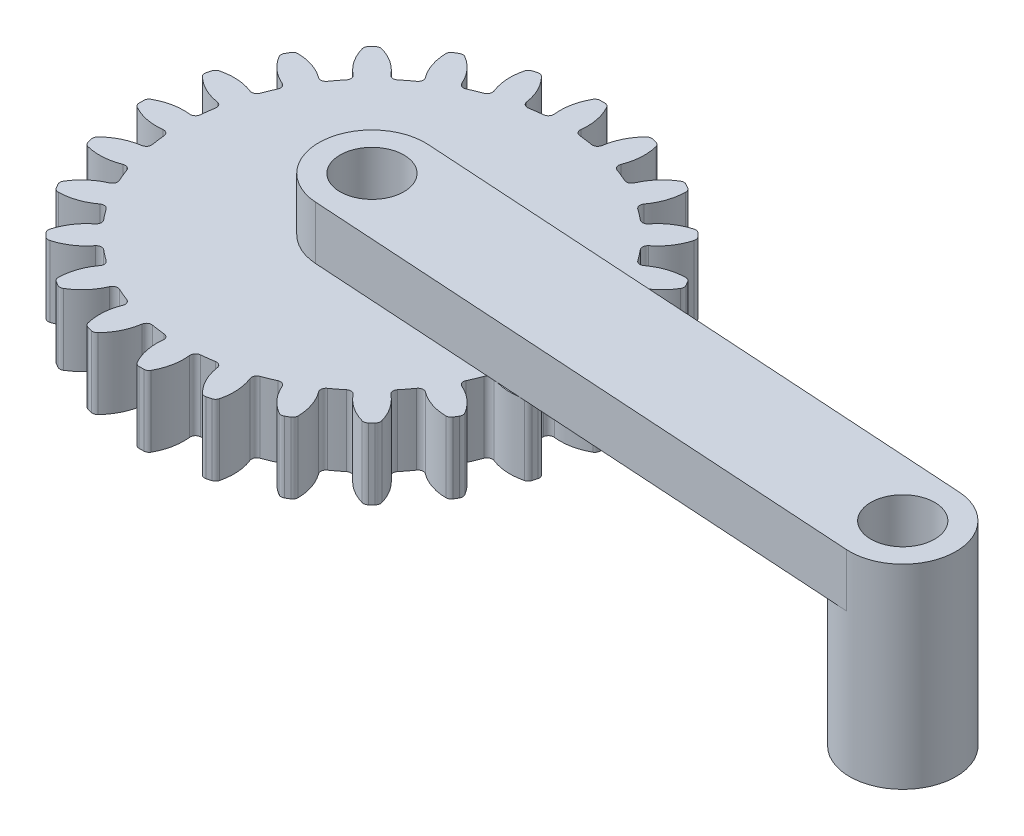
SolidWorks part; units mm, degrees
note: '?' marks a value the reader was unsure of. The reader was unsure of these and kept them because the rebuilt part matched: shared geometry of "Sketch2<5>".
ref_plane "Front Plane" through (0, 0, 0) normal (0, 0, 1) x (1, 0, 0)
ref_plane "Top Plane" through (0, 0, 0) normal (0, 1, 0) x (1, 0, 0)
ref_plane "Right Plane" through (0, 0, 0) normal (1, 0, 0) x (0, 0, -1)
sketch "Sketch2" plane through (0, 0, 0) normal (0, 1, 0) x (1, 0, 0)
  line L0 (0, 0) -> (0, 10.4648) construction
  line L1 (0.3, 13) -> (-0.3, 13)
  circle A0 centre (0, 0) radius 10.75
  circle A1 centre (0, 0) radius 13 construction
  arc A2 (-0.3, 13) -> (-0.7, 10.7272) centre (2.2248, 11.3841) ccw
  arc A3 (0.3, 13) -> (0.7, 10.7272) centre (-2.2248, 11.3841) cw
  circle A4 centre (0, 0) radius 2.55
  arc A5 (-0.7, 10.7272) -> (0.7, 10.7272) centre (0, 0) cw
  point P10 (0, 13)
  dimension "D1" = 21.5
  dimension "D2" = 26
  dimension "D5" = 5.1
  dimension "D3" = 0.6
  dimension "D4" = 0.7
extrude "Boss-Extrude1" add sketch "Sketch2" along normal blind 4
extrude "Boss-Extrude2" add sketch "Sketch2<5>" along normal blind 4 contours A3 L1 A2 A0
sketch "Sketch2<5>" plane through (0, 0, 0) normal (0, 1, 0) x (1, 0, 0) same geometry as "Sketch2"
pattern_circular "CirPattern2" count 24 over 360 about axis through (0, 0, 0) along (0, 1, 0) of "Boss-Extrude2"
sketch "Sketch3" plane through (0, 4, 0) normal (0, 1, 0) x (1, 0, 0)
  line L0 (31.9374, -2) -> (0, 0) construction
  line L1 (31.7499, -4.9941) -> (-0.1875, -2.9941)
  line L2 (32.1249, 0.9941) -> (0.1875, 2.9941)
  line L3 (0, 0) -> (16.4404, 0) construction
  arc A0 (31.7499, -4.9941) -> (32.1249, 0.9941) centre (31.9374, -2) ccw
  arc A1 (0.1875, 2.9941) -> (-0.1875, -2.9941) centre (0, 0) ccw
  circle A2 centre (0, 0) radius 1.8
  circle A3 centre (31.9374, -2) radius 1.8
  point P2 (15.9687, -1)
  dimension "D1" = 3
  dimension "D3" = 3.6
  dimension "D2" = 32
  dimension "D4" = 2
extrude "Boss-Extrude3" add sketch "Sketch3" along normal blind 3
sketch "Sketch4" plane through (0, 4, 0) normal (0, -1, 0) x (1, 0, 0)
  circle A0 centre (31.9374, 2) radius 1.8
  circle A1 centre (31.9374, 2) radius 3
  dimension "D1" = 3.6
extrude "Boss-Extrude4" add sketch "Sketch4" along normal blind 8
sketch "Sketch5" plane through (0, 4, 0) normal (0, -1, 0) x (1, 0, 0)
  circle A0 centre (0, 0) radius 1.8
  circle A1 centre (0, 0) radius 2.55
  dimension "D1" = 3.6
extrude "Boss-Extrude5" add sketch "Sketch5" along normal blind 3
fillet "Fillet1" radius 0.3 96 edges at (4.7574, 2, 9.64) (6.2402, 2, 11.4083) (6.7598, 2, 11.1083) (5.9698, 2, 8.94) (2.1003, 2, 10.5428) (3.0749, 2, 12.6347) (3.6544, 2, 12.4794) (3.4525, 2, 10.1805) (-0.7, 2, 10.7272) (-0.3, 2, 13) (0.3, 2, 13) (0.7, 2, 10.7272) (0.7, 2, -10.7272) (-3.4525, 2, 10.1805) (-3.6544, 2, 12.4794) (-3.0749, 2, 12.6347) (-2.1003, 2, 10.5428) (0.3, 2, -13) (-0.3, 2, -13) (-5.9698, 2, 8.94) (-6.7598, 2, 11.1083) (-6.2402, 2, 11.4083) (-4.7574, 2, 9.64) (-0.7, 2, -10.7272) (-8.0802, 2, 7.0903) (-9.4045, 2, 8.9803) (-8.9803, 2, 9.4045) (-7.0903, 2, 8.0802) (-9.64, 2, 4.7574) (-11.4083, 2, 6.2402) (-11.1083, 2, 6.7598) (-8.94, 2, 5.9698) (-10.5428, 2, 2.1003) (-12.6347, 2, 3.0749) (-12.4794, 2, 3.6544) (-10.1805, 2, 3.4525) (-10.7272, 2, -0.7) (-13, 2, -0.3) (-13, 2, 0.3) (-10.7272, 2, 0.7) (-10.1805, 2, -3.4525) (-12.4794, 2, -3.6544) (-12.6347, 2, -3.0749) (-10.5428, 2, -2.1003) (-8.94, 2, -5.9698) (-11.1083, 2, -6.7598) (-11.4083, 2, -6.2402) (-9.64, 2, -4.7574) (-7.0903, 2, -8.0802) (-8.9803, 2, -9.4045) (-9.4045, 2, -8.9803) (-8.0802, 2, -7.0903) (-4.7574, 2, -9.64) (-6.2402, 2, -11.4083) (-6.7598, 2, -11.1083) (-5.9698, 2, -8.94) (10.7272, 2, 0.7) (13, 2, 0.3) (13, 2, -0.3) (10.7272, 2, -0.7) (10.5428, 2, -2.1003) (12.6347, 2, -3.0749) (12.4794, 2, -3.6544) (10.1805, 2, -3.4525) (9.64, 2, -4.7574) (11.4083, 2, -6.2402) (11.1083, 2, -6.7598) (8.94, 2, -5.9698) (8.0802, 2, -7.0903) (9.4045, 2, -8.9803) (8.9803, 2, -9.4045) (7.0903, 2, -8.0802) (5.9698, 2, -8.94) (6.7598, 2, -11.1083) (6.2402, 2, -11.4083) (4.7574, 2, -9.64) (3.4525, 2, -10.1805) (3.6544, 2, -12.4794) (3.0749, 2, -12.6347) (2.1003, 2, -10.5428) (-2.1003, 2, -10.5428) (-3.0749, 2, -12.6347) (-3.6544, 2, -12.4794) (-3.4525, 2, -10.1805) (10.1805, 2, 3.4525) (12.4794, 2, 3.6544) (12.6347, 2, 3.0749) (10.5428, 2, 2.1003) (8.94, 2, 5.9698) (11.1083, 2, 6.7598) (11.4083, 2, 6.2402) (9.64, 2, 4.7574) (7.0903, 2, 8.0802) (8.9803, 2, 9.4045) (9.4045, 2, 8.9803) (8.0802, 2, 7.0903)
sketch "Sketch6" plane through (0, 0, 0) normal (0, -1, 0) x (1, 0, 0)
  circle A0 centre (0, 0) radius 1.8
  circle A1 centre (0, 0) radius 3
  dimension "D1" = 6
  dimension "D2" = 3.6
extrude "Boss-Extrude6" add sketch "Sketch6" along normal blind 4
sketch "Sketch7" plane through (0, 0, 0) normal (0, 0, 1) x (1, 0, 0)
  line L0 (-13, 0) -> (-13, 4) construction
  line L1 (-10.4641, 4) -> (-12.3072, 4) construction
  arc A0 (-13, 2) -> (-9, -0.4053) centre (-9.1861, 3.8139) ccw
  dimension "D1" = 2
  dimension "D2" = 4
ref_axis "Axis1" through (0, 11.6, 0) along (0, -1, 0)?
other "Cut-Revolve-Thin1" [suppressed] parameters "D1"=360, "D3"=10, "D4"=10, "D7"=0
